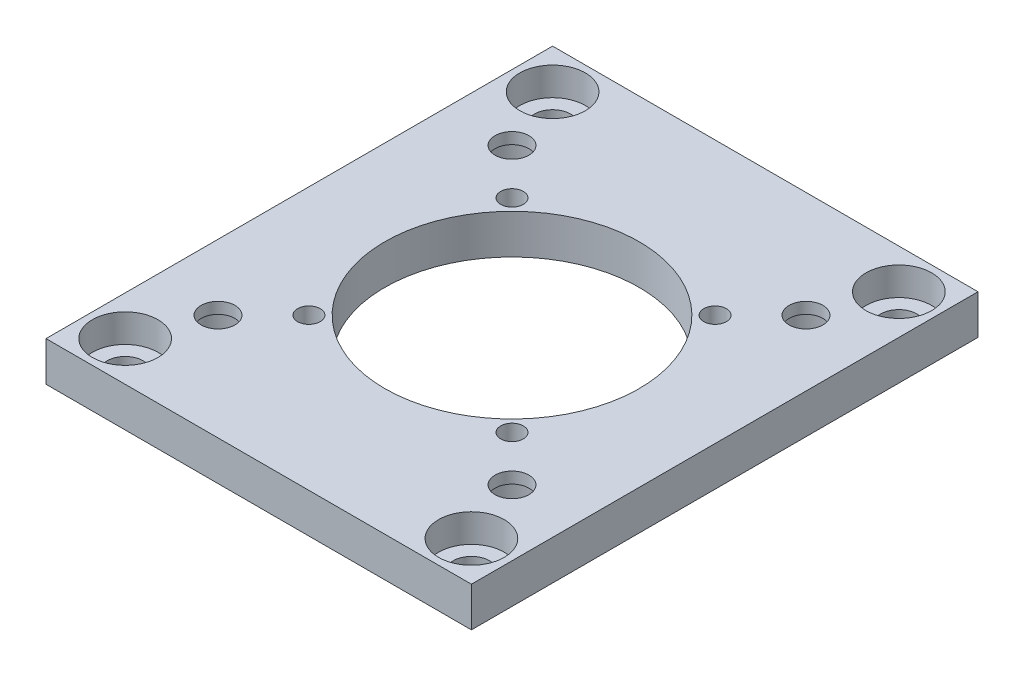
SolidWorks part; units mm, degrees
ref_plane "Front Plane" through (0, 0, 0) normal (0, 0, 1) x (1, 0, 0)
ref_plane "Top Plane" through (0, 0, 0) normal (0, 1, 0) x (1, 0, 0)
ref_plane "Right Plane" through (0, 0, 0) normal (1, 0, 0) x (0, 0, -1)
sketch "Sketch2" plane through (0, 0, 0) normal (0, 1, 0) x (1, 0, 0)
  line L0 (0, -13) -> (0, 13) construction
  line L1 (-13, 13) -> (13, 13) construction
  line L2 (-13, 13) -> (-13, -13) construction
  line L3 (-13, -13) -> (13, -13) construction
  line L4 (13, 13) -> (13, -13) construction
  line L5 (-13, 0) -> (13, 0) construction
  line L7 (-18.8109, -22.4) -> (18.8109, -22.4)
  line L9 (-18.8109, 22.4) -> (18.8109, 22.4)
  line L10 (18.8109, -22.4) -> (18.8109, 22.4)
  line L11 (-18.8109, -22.4) -> (18.8109, 22.4) construction
  line L12 (-18.8109, 22.4) -> (18.8109, -22.4) construction
  line L15 (-18.8109, 22.4) -> (-18.8109, -22.4)
  circle A0 centre (0, 0) radius 11.25
  circle A1 centre (-13, 13) radius 1.5
  circle A2 centre (13, 13) radius 1.5
  circle A3 centre (13, -13) radius 1.5
  circle A4 centre (-13, -13) radius 1.5
  circle A5 centre (8.98, 8.98) radius 1
  circle A6 centre (-8.98, 8.98) radius 1
  circle A7 centre (8.98, -8.98) radius 1
  circle A8 centre (-8.98, -8.98) radius 1
  circle A9 centre (-15.31, 18.9) radius 1.6
  circle A10 centre (15.31, 18.9) radius 1.6
  circle A11 centre (15.31, -18.9) radius 1.6
  circle A12 centre (-15.31, -18.9) radius 1.6
  point P15 (0, 0)
  dimension "D1" = 22.5
  dimension "D2" = 3
  dimension "D6" = 2
  dimension "D9" = 3.5
  dimension "D10" = 3.2
  dimension "D11" = 30.62
  dimension "D7" = 17.96
  dimension "D3" = 26
  dimension "D4" = 37.6219
  dimension "D5" = 44.8
  dimension "D8" = 8.98
extrude "Boss-Extrude1" add sketch "Sketch2" along normal blind 3.5
sketch "Sketch4" plane through (0, 0, 0) normal (0, -1, 0) x (1, 0, 0)
  line L0 (-11.25, 0) -> (11.25, 0) construction
  line L1 (0, -11.25) -> (0, 11.25) construction
  circle A0 centre (-13, -13) radius 2.9
  circle A1 centre (0, 0) radius 11.25 construction
  circle A2 centre (13, -13) radius 2.9
  circle A3 centre (13, 13) radius 2.9
  circle A4 centre (-13, 13) radius 2.9
  dimension "D1" = 5.8
extrude "Cut-Extrude1" cut sketch "Sketch4" against normal blind 2.5
sketch "Sketch6" plane through (0, 3.5, 0) normal (0, 1, 0) x (1, 0, 0)
  line L0 (0, -22.4) -> (0, 22.4) construction
  line L1 (18.8109, 22.4) -> (-18.8109, 22.4) construction
  line L3 (18.8109, 0) -> (-18.8109, 0) construction
  line L6 (18.8109, -22.4) -> (18.8109, 22.4) construction
  line L8 (-18.8109, -22.4) -> (18.8109, -22.4) construction
  line L9 (-18.8109, 22.4) -> (-18.8109, -22.4) construction
  circle A0 centre (-15.31, 18.9) radius 2.9
  circle A1 centre (15.31, -18.9) radius 1.6 construction
  circle A2 centre (15.31, -18.9) radius 2.9
  circle A3 centre (15.31, 18.9) radius 2.9
  circle A4 centre (-15.31, -18.9) radius 2.9
  circle A5 centre (-15.31, -18.9) radius 1.6 construction
  circle A6 centre (-15.31, -18.9) radius 1.6
  circle A9 centre (15.31, 18.9) radius 1.5 construction
  circle M16 centre (-15.31, 18.9) radius 1.6
  circle M17 centre (15.31, 18.9) radius 1.6
  circle M18 centre (15.31, -18.9) radius 1.6
  circle M41 centre (-15.31, -18.9) radius 1.6
  dimension "D1" = 5.8
  dimension "D2" = 5.8
  dimension "D3" = 5.8
extrude "Cut-Extrude2" cut sketch "Sketch6" against normal blind 2.5 contours A2 M18 | M17 | A0 M16 | A4 M41 region at (-18.128, 3.5, -18.9) region at (12.492, 3.5, 18.9) region at (12.492, 3.5, -18.9) region at (-18.128, 3.5, 18.9)
